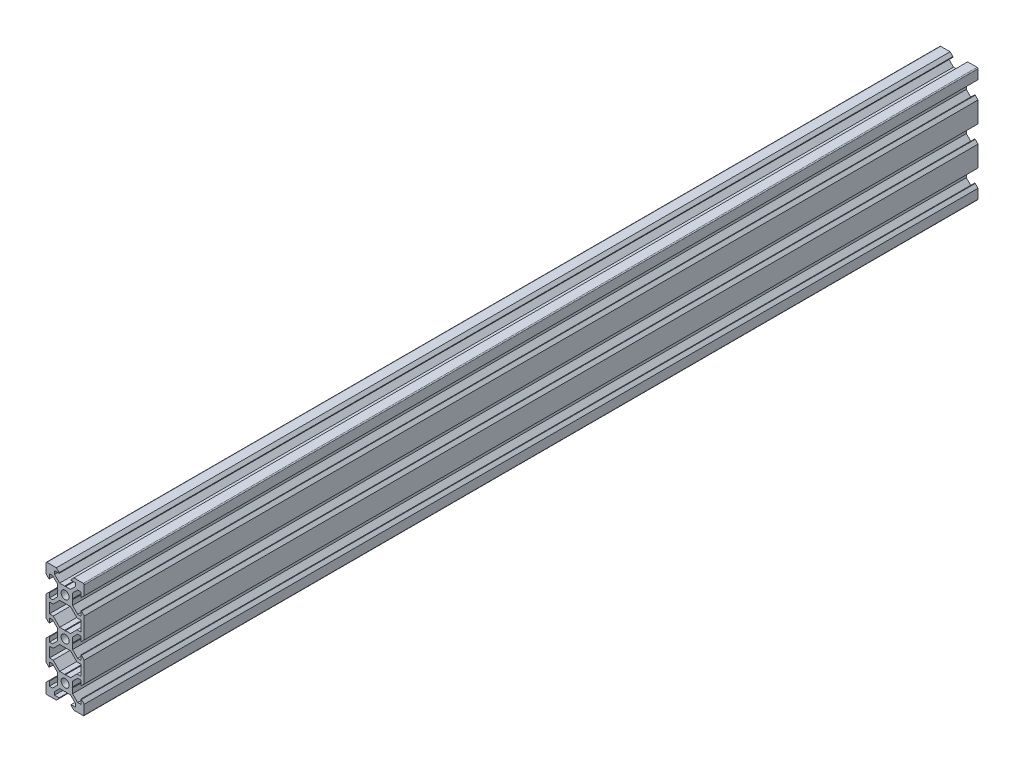
SolidWorks part; units mm, degrees
ref_plane "Plan de face" through (0, 0, 0) normal (0, 0, 1) x (1, 0, 0)
ref_plane "Plan de dessus" through (0, 0, 0) normal (0, 1, 0) x (1, 0, 0)
ref_plane "Plan de droite" through (0, 0, 0) normal (1, 0, 0) x (0, 0, -1)
ref_axis "Axe" through (0, 0, -13.782) along (0, 0, 1)
sketch "Esquisse1" plane through (0, 0, 0) normal (0, 0, 1) x (1, 0, 0)
  line L0 (0, 27.6392) -> (0, -27.6392) construction
  line L1 (-33.6074, 0) -> (33.6074, 0) construction
  line L2 (0, 0) -> (-22.2114, 22.2114) construction
  line L3 (-9.5, 10) -> (-4.58, 10)
  line L4 (-4.58, 10) -> (-3.125, 8.545)
  line L5 (-3.125, 8.545) -> (-3.125, 8.2)
  line L6 (-3.125, 8.2) -> (-5.5, 8.2)
  line L7 (-2.8393, 3.9) -> (-5.5, 6.5607)
  line L8 (-2.8393, 3.9) -> (-0.21, 3.9)
  line L9 (-5.5, 6.5607) -> (-5.5, 8.2)
  line L10 (0, 3.69) -> (0, 2.1)
  line L11 (-3.9, 2.8393) -> (-6.5607, 5.5)
  line L12 (-8.545, 3.125) -> (-8.2, 3.125)
  line L13 (-8.2, 3.125) -> (-8.2, 5.5)
  line L14 (-6.5607, 5.5) -> (-8.2, 5.5)
  line L15 (-10, 4.58) -> (-8.545, 3.125)
  line L16 (-10, 9.5) -> (-10, 4.58)
  line L17 (-0.21, 3.9) -> (0, 3.69)
  line L18 (-3.9, 2.8393) -> (-3.9, 0.21)
  line L19 (-6.2393, -12.7) -> (-8.2, -12.7)
  line L20 (-3.9, 0.21) -> (-3.69, 0)
  line L21 (-0.21, -3.9) -> (0, -3.69)
  line L22 (0, -3.69) -> (0, -2.1)
  line L23 (-6.5607, -5.5) -> (-8.2, -5.5)
  line L24 (-2.8393, -3.9) -> (-0.21, -3.9)
  line L25 (-8.545, -3.125) -> (-8.2, -3.125)
  line L26 (-10, -4.58) -> (-8.545, -3.125)
  line L27 (-8.2, -3.125) -> (-8.2, -5.5)
  line L28 (-2.8393, -3.9) -> (-6.2393, -7.3)
  line L29 (-3.9, -2.8393) -> (-6.5607, -5.5)
  line L30 (-3.9, -2.8393) -> (-3.9, -0.21)
  line L31 (-3.9, -0.21) -> (-3.69, 0)
  line L32 (-6.2393, -7.3) -> (-8.2, -7.3)
  line L33 (-8.2, -7.3) -> (-8.2, -12.7)
  line L34 (-8.2, -10) -> (-10, -10) construction
  line L35 (-10, -15.42) -> (-10, -4.58)
  line L36 (-3.9, -19.79) -> (-3.69, -20)
  line L37 (-3.9, -17.1607) -> (-3.9, -19.79)
  line L38 (-3.9, -17.1607) -> (-6.5607, -14.5)
  line L39 (-2.8393, -16.1) -> (-6.2393, -12.7)
  line L40 (-8.2, -16.875) -> (-8.2, -14.5)
  line L41 (-10, -15.42) -> (-8.545, -16.875)
  line L42 (-8.545, -16.875) -> (-8.2, -16.875)
  line L43 (-2.8393, -16.1) -> (-0.21, -16.1)
  line L44 (-6.5607, -14.5) -> (-8.2, -14.5)
  line L45 (0, -16.31) -> (0, -17.9)
  line L46 (-0.21, -16.1) -> (0, -16.31)
  line L47 (-8.2, -30) -> (-10, -30) construction
  line L48 (-3.69, -20) -> (0, -20) construction
  line L49 (-0.21, -23.9) -> (0, -23.69)
  line L50 (0, -23.69) -> (0, -22.1)
  line L51 (-6.5607, -25.5) -> (-8.2, -25.5)
  line L52 (-2.8393, -23.9) -> (-0.21, -23.9)
  line L53 (-8.545, -23.125) -> (-8.2, -23.125)
  line L54 (-10, -24.58) -> (-8.545, -23.125)
  line L55 (-8.2, -23.125) -> (-8.2, -25.5)
  line L56 (-2.8393, -23.9) -> (-6.2393, -27.3)
  line L57 (-3.9, -22.8393) -> (-6.5607, -25.5)
  line L58 (-3.9, -22.8393) -> (-3.9, -20.21)
  line L59 (-3.9, -20.21) -> (-3.69, -20)
  line L60 (-10, -24.58) -> (-10, -35.42)
  line L61 (-8.2, -32.7) -> (-8.2, -27.3)
  line L62 (-6.2393, -32.7) -> (-8.2, -32.7)
  line L63 (-3.9, -39.79) -> (-3.69, -40)
  line L64 (-3.9, -37.1607) -> (-3.9, -39.79)
  line L65 (-3.9, -37.1607) -> (-6.5607, -34.5)
  line L66 (-2.8393, -36.1) -> (-6.2393, -32.7)
  line L67 (-8.2, -36.875) -> (-8.2, -34.5)
  line L68 (-10, -35.42) -> (-8.545, -36.875)
  line L69 (-8.545, -36.875) -> (-8.2, -36.875)
  line L70 (-2.8393, -36.1) -> (-0.21, -36.1)
  line L71 (-6.5607, -34.5) -> (-8.2, -34.5)
  line L72 (0, -36.31) -> (0, -37.9)
  line L73 (-0.21, -36.1) -> (0, -36.31)
  line L74 (-3.9, -40.21) -> (-3.69, -40)
  line L75 (-6.2393, -27.3) -> (-8.2, -27.3)
  line L76 (-3.9, -42.8393) -> (-3.9, -40.21)
  line L77 (-0.21, -43.9) -> (0, -43.69)
  line L78 (-10, -49.5) -> (-10, -44.58)
  line L79 (-10, -44.58) -> (-8.545, -43.125)
  line L80 (-6.5607, -45.5) -> (-8.2, -45.5)
  line L81 (-8.2, -43.125) -> (-8.2, -45.5)
  line L82 (-8.545, -43.125) -> (-8.2, -43.125)
  line L83 (-3.9, -42.8393) -> (-6.5607, -45.5)
  line L84 (0, -43.69) -> (0, -42.1)
  line L85 (-5.5, -46.5607) -> (-5.5, -48.2)
  line L86 (-2.8393, -43.9) -> (-0.21, -43.9)
  line L87 (-2.8393, -43.9) -> (-5.5, -46.5607)
  line L88 (-3.125, -48.2) -> (-5.5, -48.2)
  line L89 (-3.125, -48.545) -> (-3.125, -48.2)
  line L90 (-4.58, -50) -> (-3.125, -48.545)
  line L91 (-9.5, -50) -> (-4.58, -50)
  arc A0 (0, -2.1) -> (0, 2.1) centre (0, 0) cw
  arc A1 (-9.5, 10) -> (-10, 9.5) centre (-9.5, 9.5) ccw
  arc A2 (0, -37.9) -> (0, -42.1) centre (0, -40) ccw
  arc A3 (-9.5, -50) -> (-10, -49.5) centre (-9.5, -49.5) cw
  arc A4 (0, -17.9) -> (0, -22.1) centre (0, -20) ccw
  point P4 (0, 0)
  point P7 (0, 0)
  point P30 (-10, 10)
  point P60 (0, -20)
  point P111 (-10, -50)
  dimension "D5" = 11
  dimension "D2" = 2.1
  dimension "D3" = 6.25
  dimension "D10" = 0.5
  dimension "D4" = 9.16
  dimension "D6" = 1.5
  dimension "D7" = 1.8
  dimension "D8" = 4.3
  dimension "D9" = 20
  dimension "D11" = 0.42
  dimension "D12" = 10
  dimension "D13" = 1.8
extrude "Boss.-Extru.1" add sketch "Esquisse1" along normal blind 467.7
sketch "Esquisse3" plane through (0, 0, 467.7) normal (0, 0, 1) x (1, 0, 0)
  line L0 (0, 0) -> (-9.8536, 9.8536) construction
  line L1 (-8.2, 8.2) -> (-8.2, 6.57)
  line L2 (-8.2, 6.57) -> (-7.54, 6.57)
  line L3 (-7.54, 6.57) -> (-6.57, 7.54)
  line L4 (-8.2, 3.125) -> (-8.2, 5.5) construction
  line L5 (-6.57, 8.2) -> (-6.57, 7.54)
  line L6 (-8.2, 8.2) -> (-6.57, 8.2)
  line L7 (-5.5, 6.5607) -> (-5.5, 8.2) construction
  line L8 (-3.69, -20) -> (0, -20) construction
  line L9 (-8.2, -48.2) -> (-6.57, -48.2)
  line L10 (-6.57, -48.2) -> (-6.57, -47.54)
  line L11 (-7.54, -46.57) -> (-6.57, -47.54)
  line L12 (-8.2, -46.57) -> (-7.54, -46.57)
  line L13 (-8.2, -48.2) -> (-8.2, -46.57)
  arc A0 (-9.5, 10) -> (-10, 9.5) centre (-9.5, 9.5) ccw construction
  point P13 (-7.055, 7.055)
  point P14 (-6.57, 7.87)
  point P26 (-7.055, -47.055)
  dimension "D1" = 1.07
extrude "Enlèv. mat.-Extru.1" [suppressed] cut sketch "Esquisse3" against normal through all
mirror "Symétrie1" about plane through (0, 3.69, 467.7) normal (-1, 0, 0) of "Enlèv. mat.-Extru.1", "Boss.-Extru.1"
